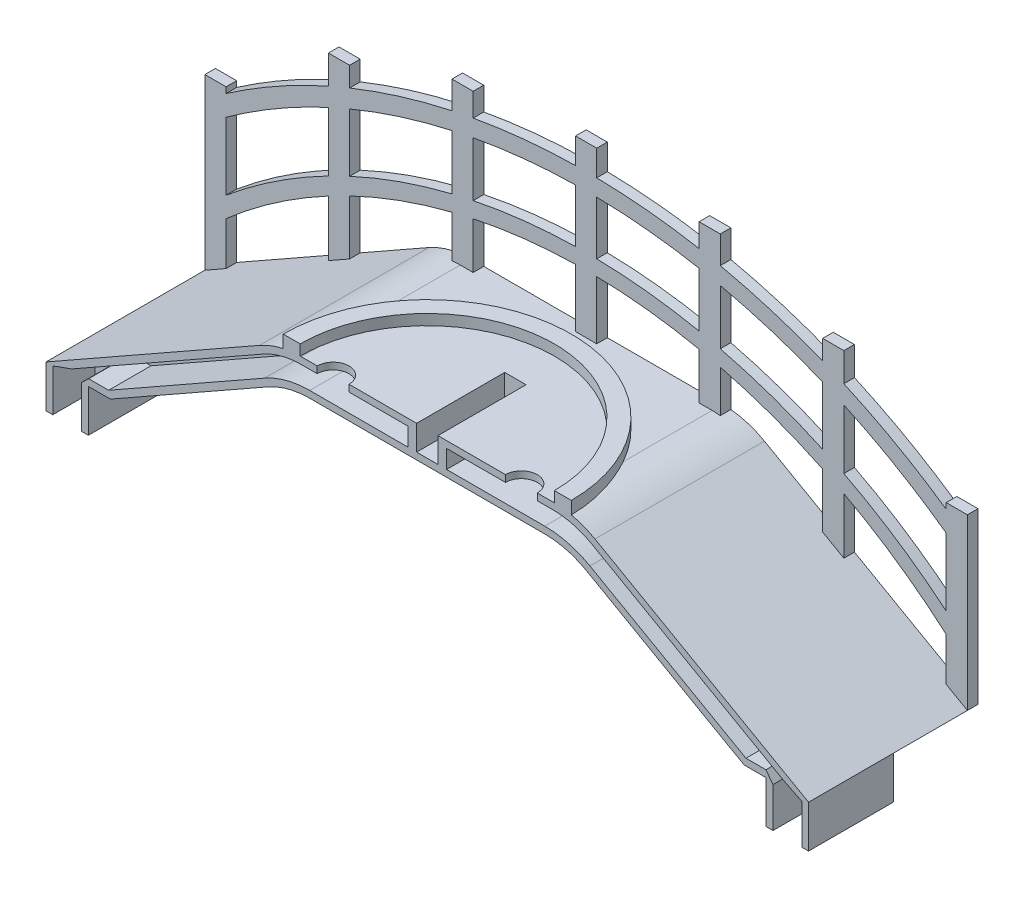
SolidWorks part; units mm, degrees
ref_plane "Front Plane" through (0, 0, 0) normal (0, 0, 1) x (1, 0, 0)
ref_plane "Top Plane" through (0, 0, 0) normal (0, 1, 0) x (1, 0, 0)
ref_plane "Right Plane" through (0, 0, 0) normal (1, 0, 0) x (0, 0, -1)
sketch "Sketch5" plane through (0, 0, 0) normal (0, 0, 1) x (1, 0, 0)
  line L0 (1.175, -2.0712) -> (16.6334, 6.6983)
  line L1 (19.1382, 9.9064) -> (38.0118, 9.9064)
  line L2 (0, 0) -> (16.005, 9.0795)
  line L3 (41.145, 9.0795) -> (57.15, 0)
  line L4 (0, 0) -> (17.4625, 0) construction
  line L5 (57.15, 0) -> (39.6875, 0) construction
  line L6 (19.7666, 7.5251) -> (37.3834, 7.5251)
  line L7 (40.5166, 6.6983) -> (55.975, -2.0712)
  line L8 (0, 0) -> (4.826, 0)
  line L9 (57.15, 0) -> (52.324, 0)
  line L10 (0, 0) -> (0, 9.525)
  line L11 (57.15, 0) -> (57.15, 9.525)
  line L12 (28.575, 9.9064) -> (28.575, 19.4314) construction
  line L13 (28.575, 9.9064) -> (28.575, 6.7314) construction
  line L14 (0, 0) -> (1.5875, 0)
  line L15 (0, 0) -> (0, 12.7)
  line L16 (0, 12.7) -> (1.5875, 12.7)
  line L17 (1.5875, 0) -> (1.5875, 12.7)
  line L18 (29.3687, 6.7314) -> (27.7812, 6.7314)
  line L19 (29.3687, 6.7314) -> (29.3687, 22.6064)
  line L20 (29.3687, 22.6064) -> (27.7812, 22.6064)
  line L21 (27.7812, 6.7314) -> (27.7812, 22.6064)
  line L22 (1.5875, 9.2118) -> (9.2604, 9.2118) construction
  line L23 (9.2604, 18.7284) -> (10.8479, 18.7284)
  line L24 (9.2604, 18.7284) -> (9.2604, 2.8534)
  line L25 (9.2604, 2.8534) -> (10.8479, 2.8534)
  line L26 (10.8479, 18.7284) -> (10.8479, 2.8534)
  line L27 (18.5208, 21.6681) -> (20.1083, 21.6681)
  line L28 (18.5208, 21.6681) -> (18.5208, 5.7931)
  line L29 (18.5208, 5.7931) -> (20.1083, 5.7931)
  line L30 (20.1083, 21.6681) -> (20.1083, 5.7931)
  line L31 (10.8479, 8.208) -> (18.5208, 8.208) construction
  line L32 (20.1083, 13.1596) -> (27.7812, 13.1596) construction
  line L33 (10.0542, 18.7284) -> (10.0542, 15.5534) construction
  line L34 (19.3146, 21.6681) -> (19.3146, 18.4931) construction
  line L35 (57.15, 0) -> (52.324, 0)
  line L36 (38.6292, 21.6681) -> (37.0417, 21.6681)
  line L37 (38.6292, 21.6681) -> (38.6292, 5.7931)
  line L38 (37.0417, 21.6681) -> (37.0417, 5.7931)
  line L39 (38.6292, 5.7931) -> (37.0417, 5.7931)
  line L40 (47.8896, 2.8534) -> (46.3021, 2.8534)
  line L41 (47.8896, 18.7284) -> (46.3021, 18.7284)
  line L42 (46.3021, 18.7284) -> (46.3021, 2.8534)
  line L43 (47.8896, 18.7284) -> (47.8896, 2.8534)
  line L44 (57.15, 12.7) -> (55.5625, 12.7)
  line L45 (57.15, 0) -> (57.15, 12.7)
  line L46 (57.15, 0) -> (57.15, 9.525)
  line L47 (55.5625, 0) -> (55.5625, 12.7)
  line L48 (18.0909, 7.5251) -> (39.0591, 7.5251) construction
  line L49 (39.0591, 7.5251) -> (55.975, -2.0712) construction
  line L50 (17.4625, 9.9064) -> (39.6875, 9.9064) construction
  line L51 (39.6875, 9.9064) -> (57.15, 0) construction
  line L52 (1.175, -2.0712) -> (18.0909, 7.5251) construction
  line L53 (0, 0) -> (17.4625, 9.9064) construction
  arc A0 (0, 9.525) -> (57.15, 9.525) centre (28.575, -26.7342) cw
  arc A1 (0, 11.1125) -> (57.15, 11.1125) centre (28.575, -26.7342) cw
  arc A2 (37.3834, 7.5251) -> (40.5166, 6.6983) centre (37.3834, 1.1751) cw
  arc A3 (38.0118, 9.9064) -> (41.145, 9.0795) centre (38.0118, 3.5564) cw
  arc A4 (16.6334, 6.6983) -> (19.7666, 7.5251) centre (19.7666, 1.1751) cw
  arc A5 (19.1382, 9.9064) -> (16.005, 9.0795) centre (19.1382, 3.5564) ccw
  point P47 (57.15, 10.9464)
  point P65 (39.6875, 9.9064)
  dimension "D12" = 6.35
  dimension "D1" = 57.15
  dimension "D3" = 2.3813
  dimension "D4" = 9.525
  dimension "D5" = 1.5875
  dimension "D6" = 12.7
  dimension "D7" = 1.5875
  dimension "D8" = 15.875
  dimension "D9" = 12.7
  dimension "D10" = 3.175
  dimension "D11" = 1.5875
extrude "Boss-Extrude1" add sketch "Sketch5" along normal blind 12.7 contours L25 L24 L2 L17 L8 L0 | L8 L17 L2 | L26 L2 L24 L25 L0 | L28 A5 L2 L26 L0 A4 | L1 A5 L28 A4 L6 L30 | L1 L30 L6 L21 | L21 L6 L19 L1 | L38 L1 L19 L6 | A3 L1 L38 L6 A2 L37 | A3 L37 A2 L7 L42 L3 | L43 L3 L42 L7 L40 | L35 L47 L3 L43 L40 L7 | L47 L9 L3 region at (5.8986, 2.0945, 0) region at (10.0683, 4.3725, 0) region at (1.0583, 0.3002, 0) region at (14.6384, 6.8871, 0) region at (19.3092, 8.6975, 0) region at (23.9448, 8.7158, 0) region at (28.575, 8.7158, 0) region at (33.2052, 8.7158, 0) region at (37.8408, 8.6975, 0) region at (42.5116, 6.8871, 0) region at (47.0817, 4.3725, 0) region at (51.2514, 2.0945, 0) region at (56.0917, 0.3002, 0)
extrude "Boss-Extrude2" add sketch "Sketch5<4>" along normal blind 0.7937 separate body contours A1 L15 A0 L17 | A1 L17 A0 L24 | A1 L24 A0 L26 | A1 L26 A0 L28 | A1 L28 A0 L30 | A1 L30 A0 L21 | A1 L21 A0 L19 | A1 L19 A0 L38 | A1 L38 A0 L37 | A1 L37 A0 L42 | A1 L42 A0 L43 | A1 L43 A0 L47 | A1 L47 A0 L45 region at (0.7896, 10.9105, 0) region at (5.3546, 13.8101, 0) region at (10.0521, 16.234, 0) region at (14.65, 17.8791, 0) region at (19.3137, 19.1317, 0) region at (23.9343, 19.7758, 0) region at (28.575, 20.0576, 0) region at (33.2157, 19.7758, 0) region at (37.8363, 19.1317, 0) region at (42.5, 17.8791, 0) region at (47.0979, 16.234, 0) region at (51.7954, 13.8101, 0) region at (56.3604, 10.9105, 0)
sketch "Sketch5<4>" plane through (0, 0, 0) normal (0, 0, 1) x (1, 0, 0) same geometry as "Sketch5"
extrude "Boss-Extrude6" add sketch "Sketch5<7>" along normal blind 0.7937 contours A0 L10 L2 L17 | A1 L15 A0 L17 | L15 A1 L17 L16 | A0 L24 L2 L26 | A1 L24 A0 L26 | L24 A1 L26 L23 | L26 L2 L24 L25 L0 | L26 L0 L25 | A4 L28 L29 L30 L6 | L1 A5 L28 A4 L6 L30 | A5 L1 L30 A0 L28 | A1 L28 A0 L30 | L28 A1 L30 L27 | L21 A1 L19 L20 | A1 L21 A0 L19 | A0 L21 L1 L19 | L21 L6 L19 L1 | L21 L18 L19 L6 | L47 L9 L3 | A0 L47 L3 L11 | A1 L47 A0 L45 | L47 A1 L45 L44 | A0 L42 L3 L43 | A1 L42 A0 L43 | L42 A1 L43 L41 | L43 L3 L42 L7 L40 | L7 L42 L40 | A2 L6 L38 L39 L37 | A3 L1 L38 L6 A2 L37 | L1 A3 L37 A0 L38 | L38 A1 L37 L36 | A1 L38 A0 L37 region at (10.0683, 4.3725, 0) region at (10.5172, 3.041, 0) region at (0.7978, 5.2939, 0) region at (10.0514, 10.6257, 0) region at (0.7896, 10.9105, 0) region at (19.3237, 6.6434, 0) region at (19.3092, 8.6975, 0) region at (10.0521, 16.234, 0) region at (0.6427, 12.1428, 0) region at (19.3193, 14.1971, 0) region at (10.0049, 17.8134, 0) region at (19.3137, 19.1317, 0) region at (19.2925, 20.7184, 0) region at (28.575, 8.7158, 0) region at (28.575, 7.1283, 0) region at (28.575, 14.6677, 0) region at (28.575, 20.0576, 0) region at (28.575, 21.6463, 0) region at (37.8408, 8.6975, 0) region at (37.8263, 6.6434, 0) region at (37.8307, 14.1971, 0) region at (37.8363, 19.1317, 0) region at (37.8575, 20.7184, 0) region at (47.0986, 10.6257, 0) region at (47.0979, 16.234, 0) region at (47.1451, 17.8134, 0) region at (47.0817, 4.3725, 0) region at (46.6328, 3.041, 0) region at (56.3522, 5.2939, 0) region at (56.3604, 10.9105, 0) region at (56.5073, 12.1428, 0) region at (56.0917, 0.3002, 0)
sketch "Sketch5<7>" plane through (0, 0, 0) normal (0, 0, 1) x (1, 0, 0) same geometry as "Sketch5"
sketch "Sketch6" plane through (0, 0, 0) normal (0, 0, -1) x (-1, 0, 0)
  line L0 (-57.15, 0) -> (-57.15, 12.7) construction
  line L1 (0, 0) -> (0, 12.7) construction
  line L2 (-57.15, 4.2704) -> (-57.15, 2.6829)
  line L3 (0, 2.6829) -> (0, 4.2704)
  arc A0 (-57.15, 4.2704) -> (0, 4.2704) centre (-28.575, -26.7342) cw
  arc A1 (-57.15, 2.6829) -> (0, 2.6829) centre (-28.575, -26.7342) cw
  arc A2 (-29.3687, 19.4246) -> (-37.0417, 18.6484) centre (-28.575, -26.7342) ccw construction
  dimension "D1" = 1.5875
extrude "Boss-Extrude7" add sketch "Sketch6" against normal blind 0.7937
sketch "Sketch7" plane through (0, 0, 12.7) normal (0, 0, 1) x (1, 0, 0)
  line L0 (28.575, 9.9064) -> (19.05, 9.9064)
  line L1 (19.1382, 9.9064) -> (38.0118, 9.9064) construction
  line L2 (19.05, 9.9064) -> (19.05, 9.3984)
  line L3 (19.7666, 7.5251) -> (37.3834, 7.5251) construction
  line L4 (19.05, 9.3984) -> (38.1, 9.3984)
  line L5 (19.05, 9.3984) -> (19.05, 8.0331)
  line L6 (19.05, 8.0331) -> (38.1, 8.0331)
  line L7 (38.1, 9.3984) -> (38.1, 8.0331)
  line L20 (1.925, 0.508) -> (4.6919, 0.508)
  line L21 (4.6919, 0.508) -> (16.3827, 7.1401)
  line L22 (16.2556, 8.6377) -> (1.925, 0.508)
  line L23 (1.925, 0.508) -> (4.6919, 0.508)
  line L24 (4.6919, 0.508) -> (16.3827, 7.1401)
  line L25 (16.2556, 8.6377) -> (1.925, 0.508)
  line L37 (40.7673, 7.1401) -> (52.4581, 0.508)
  line L38 (52.4581, 0.508) -> (55.225, 0.508)
  line L39 (55.225, 0.508) -> (40.8944, 8.6377)
  line L40 (40.7673, 7.1401) -> (52.4581, 0.508)
  line L41 (52.4581, 0.508) -> (55.225, 0.508)
  line L42 (55.225, 0.508) -> (40.8944, 8.6377)
  arc A8 (19.7666, 8.0331) -> (16.3827, 7.1401) centre (19.7666, 1.1751) ccw
  arc A9 (19.1382, 9.3984) -> (16.2556, 8.6377) centre (19.1382, 3.5564) ccw
  arc A10 (19.7666, 8.0331) -> (16.3827, 7.1401) centre (19.7666, 1.1751) ccw
  arc A11 (19.1382, 9.3984) -> (16.2556, 8.6377) centre (19.1382, 3.5564) ccw
  arc A17 (40.7673, 7.1401) -> (37.3834, 8.0331) centre (37.3834, 1.1751) ccw
  arc A18 (40.8944, 8.6377) -> (38.0118, 9.3984) centre (38.0118, 3.5564) ccw
  arc A19 (40.7673, 7.1401) -> (37.3834, 8.0331) centre (37.3834, 1.1751) ccw
  arc A20 (40.8944, 8.6377) -> (38.0118, 9.3984) centre (38.0118, 3.5564) ccw
  dimension "D1" = 9.525
  dimension "D2" = 0.508
  dimension "D3" = 0.508
  dimension "D4" = 19.05
  dimension "D5" = 0.508
  dimension "D6" = 0.508
extrude "Cut-Extrude1" cut sketch "Sketch7" against normal blind 9.525 contours L7 L4 L5 L6 region at (28.575, 8.7158, 12.7)
sketch "Sketch8" plane through (0, 9.9064, 0) normal (0, 1, 0) x (1, 0, 0)
  line L0 (19.1382, -12.7) -> (38.0118, -12.7) construction
  line L1 (21.5195, -12.7) -> (19.1382, -12.7)
  line L2 (35.6305, -12.7) -> (38.0118, -12.7)
  line L4 (29.3751, -19.304) -> (27.7749, -19.304)
  line L5 (29.3751, -19.304) -> (29.3751, -6.096)
  line L6 (29.3751, -6.096) -> (27.7749, -6.096)
  line L7 (27.7749, -19.304) -> (27.7749, -6.096)
  line L8 (29.3751, -19.304) -> (27.7749, -6.096) construction
  line L9 (29.3751, -6.096) -> (27.7749, -19.304) construction
  circle A0 centre (21.5195, -12.7) radius 1.1906
  circle A1 centre (35.6305, -12.7) radius 1.1906
  point P8 (28.575, -12.7)
  line M5 (19.1382, -12.7) -> (38.0118, -12.7)
  dimension "D1" = 2.3813
  dimension "D2" = 2.3813
  dimension "D3" = 2.3813
  dimension "D4" = 1.6002
  dimension "D5" = 13.208
extrude "Cut-Extrude2" cut sketch "Sketch8" against normal blind 1.397 contours A0 L1 M5 | A1 M5 | L7 L5 L6 M5 region at (21.5195, 9.9064, 12.1947) region at (35.6305, 9.9064, 12.1947) region at (28.575, 9.9064, 9.398)
sketch "Sketch10" plane through (0, 8.0331, 0) normal (0, 1, 0) x (1, 0, 0)
  line L0 (19.05, -12.7) -> (38.1, -12.7) construction
  line L1 (30.0256, -19.9033) -> (27.1244, -19.9033)
  line L2 (30.0256, -19.9033) -> (30.0256, -5.4967)
  line L3 (30.0256, -5.4967) -> (27.1244, -5.4967)
  line L4 (27.1244, -19.9033) -> (27.1244, -5.4967)
  line L5 (30.0256, -19.9033) -> (27.1244, -5.4967) construction
  line L6 (30.0256, -5.4967) -> (27.1244, -19.9033) construction
  line L7 (27.1244, -12.7) -> (30.0256, -12.7)
  line L8 (29.3751, -19.304) -> (27.7749, -19.304)
  line L9 (29.3751, -19.304) -> (29.3751, -6.096)
  line L10 (29.3751, -6.096) -> (27.7749, -6.096)
  line L11 (27.7749, -19.304) -> (27.7749, -6.096)
  line L12 (29.3751, -19.304) -> (27.7749, -6.096) construction
  line L13 (29.3751, -6.096) -> (27.7749, -19.304) construction
  point P0 (28.575, -12.7)
  point P7 (28.575, -12.7)
  line M1 (19.05, -12.7) -> (38.1, -12.7)
extrude "Boss-Extrude8" add sketch "Sketch10" along normal blind 1.397 contours L11 L10 L9 L7 L2 L3 L4 M1 region at (29.7004, 8.0331, 12.6223)
sketch "Sketch11" plane through (0, 9.9064, 0) normal (0, 1, 0) x (1, 0, 0)
  line L0 (27.7749, -12.7) -> (29.3751, -12.7) construction
  line L1 (17.78, -12.7) -> (39.37, -12.7)
  circle A0 centre (28.575, -12.7) radius 9.525
  circle A1 centre (28.575, -12.7) radius 10.795
  line M9 (38.0118, -12.7) -> (38.0118, -0.7937)
  line M19 (19.1382, -0.7937) -> (19.1382, -12.7)
  dimension "D1" = 19.05
  dimension "D2" = 21.59
extrude "Boss-Extrude9" add sketch "Sketch11" along normal blind 0.7937 and the other way blind 0.254 contours A1 A0 M9 M19 | A1 L1 A0 M19 | L1 A1 A0 M9 region at (18.5837, 9.9064, 10.6925) region at (19.3495, 9.9064, 9.4323) region at (38.5663, 9.9064, 10.6925)
sketch "Sketch12" plane through (0, 0, 0) normal (0, -1, 0) x (1, 0, 0)
  line L1 (0, 12.7) -> (3.175, 12.7)
  line L2 (0, 12.7) -> (0, 6.35)
  line L3 (0, 6.35) -> (3.175, 6.35)
  line L4 (3.175, 12.7) -> (3.175, 6.35)
  line L5 (57.15, 12.7) -> (53.975, 12.7)
  line L6 (57.15, 12.7) -> (57.15, 6.35)
  line L7 (57.15, 6.35) -> (53.975, 6.35)
  line L8 (53.975, 12.7) -> (53.975, 6.35)
  dimension "D1" = 3.175
  dimension "D2" = 6.35
  dimension "D3" = 6.35
  dimension "D4" = 3.175
extrude "Boss-Extrude10" add sketch "Sketch12" along normal blind 3.175
sketch "Sketch14" plane through (0, 0, 12.7) normal (0, 0, 1) x (1, 0, 0)
extrude "Cut-Extrude3" cut sketch "Sketch7<4>" against normal blind 3.175 contours L5 A11 L25 L23 L24 A10 L6 | L42 A20 L7 L6 A19 L40 L41 region at (11.1062, 4.9125, 12.7) region at (46.0438, 4.9125, 12.7)
sketch "Sketch7<4>" plane through (0, 0, 12.7) normal (0, 0, 1) x (1, 0, 0) same geometry as "Sketch7"
sketch "Sketch15" plane through (0, 0, 12.7) normal (0, 0, 1) x (1, 0, 0)
  line L0 (1.925, 0.508) -> (0.508, 0)
  line L1 (0.508, 0) -> (0.508, -3.175)
  line L2 (3.175, -3.175) -> (0, -3.175) construction
  line L3 (3.195, 0.508) -> (2.667, 0)
  line L4 (2.667, 0) -> (2.667, -3.175)
  line L5 (55.225, 0.508) -> (56.642, -0.1943)
  line L6 (56.642, -0.1943) -> (56.642, -3.175)
  line L7 (57.15, -3.175) -> (53.975, -3.175) construction
  line L8 (53.955, 0.508) -> (54.483, -0.1943)
  line L9 (52.4581, 0.508) -> (55.225, 0.508) construction
  line L10 (54.483, -0.1943) -> (54.483, -3.175)
  line L11 (54.483, -3.175) -> (56.642, -3.175)
  line L12 (0.508, -3.175) -> (2.667, -3.175)
  line L13 (0, -3.175) -> (0, 0) construction
  line L14 (3.175, -3.175) -> (3.175, 0) construction
  line L16 (57.15, -3.175) -> (57.15, 0) construction
  line L17 (53.975, -3.175) -> (53.975, 0) construction
  line L18 (1.925, 0.508) -> (4.6919, 0.508) construction
  line L19 (1.925, 0.508) -> (3.195, 0.508)
  line L20 (53.955, 0.508) -> (55.225, 0.508)
  dimension "D1" = 0.508
  dimension "D2" = 0.508
  dimension "D3" = 0.508
  dimension "D4" = 0.508
  dimension "D5" = 1.27
  dimension "D6" = 1.27
extrude "Cut-Extrude4" cut sketch "Sketch15" against normal blind 3.175
